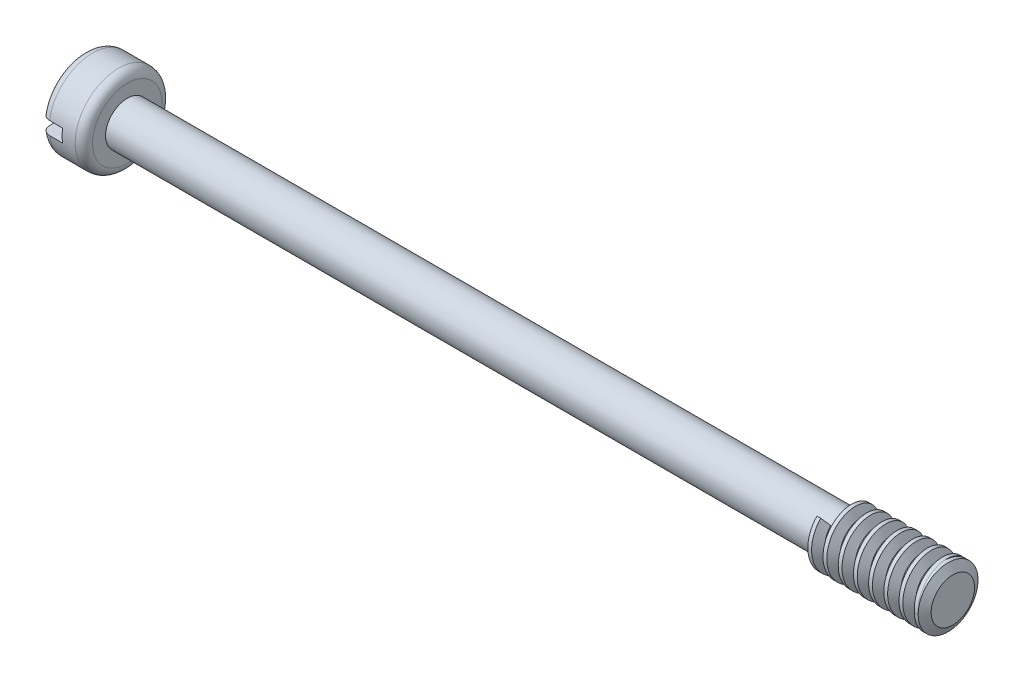
SolidWorks part; units mm, degrees
ref_plane "Front Plane" through (0, 0, 0) normal (0, 0, 1) x (1, 0, 0)
ref_plane "Top Plane" through (0, 0, 0) normal (0, 1, 0) x (1, 0, 0)
ref_plane "Right Plane" through (0, 0, 0) normal (1, 0, 0) x (0, 0, -1)
sketch "Sketch1" plane through (0, 0, 0) normal (0, 0, 1) x (1, 0, 0)
  line L0 (0, 0) -> (0, 0.8)
  line L1 (0.2, 1) -> (0.8, 1)
  line L2 (1, 0.8) -> (1, 0.5)
  line L3 (1, 0.5) -> (20, 0.5)
  line L4 (20, 0.5) -> (20, 0)
  line L5 (20, 0) -> (0, 0)
  arc A0 (0.8, 1) -> (1, 0.8) centre (0.8, 0.8) cw
  arc A1 (0, 0.8) -> (0.2, 1) centre (0.2, 0.8) cw
  point P9 (1, 1)
  point P12 (0, 1)
  dimension "D5" = 0.2
  dimension "D1" = 1
  dimension "D2" = 20
  dimension "D3" = 1
  dimension "D4" = 0.5
revolve "Revolve1" add sketch "Sketch1" angle 360 about L5
thread "Thread1" pitch 0.35 method extrude profile "Thread Profile1" start angle 0, offset 0, length 2.5, pitch 0.35, diameter 1
ref_plane "Plane1" through (20, 0, 0.5) normal (0, -1, 0) x (0, 0, 1)
sketch "Thread Profile1" plane through (20, 0, 0.5) normal (0, -1, 0) x (0, 0, 1)
  line L0 (0, 0) -> (0, 0.35) construction
  line L11 (0, 0.3063) -> (0, 0)
  line L12 (0, 0) -> (0.1894, 0.1094)
  line L13 (0.1894, 0.1094) -> (0.1894, 0.1969)
  line L15 (0.1894, 0.1969) -> (0, 0.3063)
  line L17 (0.1894, 0.1531) -> (0, 0.1531) construction
  point P3 (0, 0)
  dimension "Pitch" = 0.35
  dimension "Profile_Angle" = 60
  dimension "Profile_Land" = 0.0875
  dimension "Profile_Height" = 0.1894
sketch "Sketch5" plane through (0, 0, 0) normal (0, -1, 0) x (1, 0, 0)
  line L0 (17.4995, 0.3117) -> (17.1933, 0.3118) construction
  line L1 (17.3026, 0.4299) -> (17.3902, 0.4299) construction
  line L2 (17.1933, 0.3118) -> (17.3026, 0.4299) construction
  line L3 (17.4995, 0.3117) -> (17.1933, 0.3118)
  line L4 (19.8031, 0.6894) -> (19.6937, 0.5)
  line L5 (19.6937, 0.5) -> (20, 0.5)
  line L6 (20, 0.5) -> (19.8906, 0.6894)
  line L7 (19.8906, 0.6894) -> (19.8031, 0.6894)
  line L8 (19.8031, 0.6894) -> (19.6937, 0.5)
  line L9 (19.6937, 0.5) -> (20, 0.5)
  line L10 (20, 0.5) -> (19.8906, 0.6894)
  line L11 (19.8906, 0.6894) -> (19.8031, 0.6894)
  line L12 (17.3026, 0.4299) -> (17.3902, 0.4299)
  line L13 (17.1933, 0.3118) -> (17.3026, 0.4299)
  spline S0 degree 1 poles (-3378.9187, 3669.8345) (3413.7669, -3669.048) knots -31053.176721 -31053.176721 31053.797484 31053.797484 only from (17.3902, 0.4299) to (17.4995, 0.3117) construction
  spline S1 degree 1 poles (17.3902, 0.4299) (17.4995, 0.3117) knots 0 0 1 1
  dimension "D1" = 0
revolve "Revolve2" add sketch "Sketch5" angle 360 about axis through (20, 0, 0) along (1, 0, 0)
sketch "Sketch10" plane through (0, 0, 0) normal (-1, 0, 0) x (0, 0, 1)
  line L1 (-1, 0.15) -> (1, 0.15)
  line L2 (-1, 0.15) -> (-1, -0.15)
  line L3 (-1, -0.15) -> (1, -0.15)
  line L4 (1, 0.15) -> (1, -0.15)
  line L5 (-1, 0.15) -> (1, -0.15) construction
  line L6 (-1, -0.15) -> (1, 0.15) construction
  line L7 (-0.15, 0.7858) -> (0.15, 0.7858)
  line L8 (-0.15, 0.7858) -> (-0.15, -0.7858)
  line L9 (-0.15, -0.7858) -> (0.15, -0.7858)
  line L10 (0.15, 0.7858) -> (0.15, -0.7858)
  line L11 (-0.15, 0.7858) -> (0.15, -0.7858) construction
  line L12 (-0.15, -0.7858) -> (0.15, 0.7858) construction
  circle A0 centre (0, 0) radius 0.8 construction
  circle A1 centre (0, 0) radius 1 construction
  point P0 (0, 0)
  point P6 (0, 0)
  dimension "D1" = 0.3
extrude "Cut-Extrude1" cut sketch "Sketch10" against normal blind 0.5 contours L3 L4 L1 L2 | L8 L9 L10 L7
